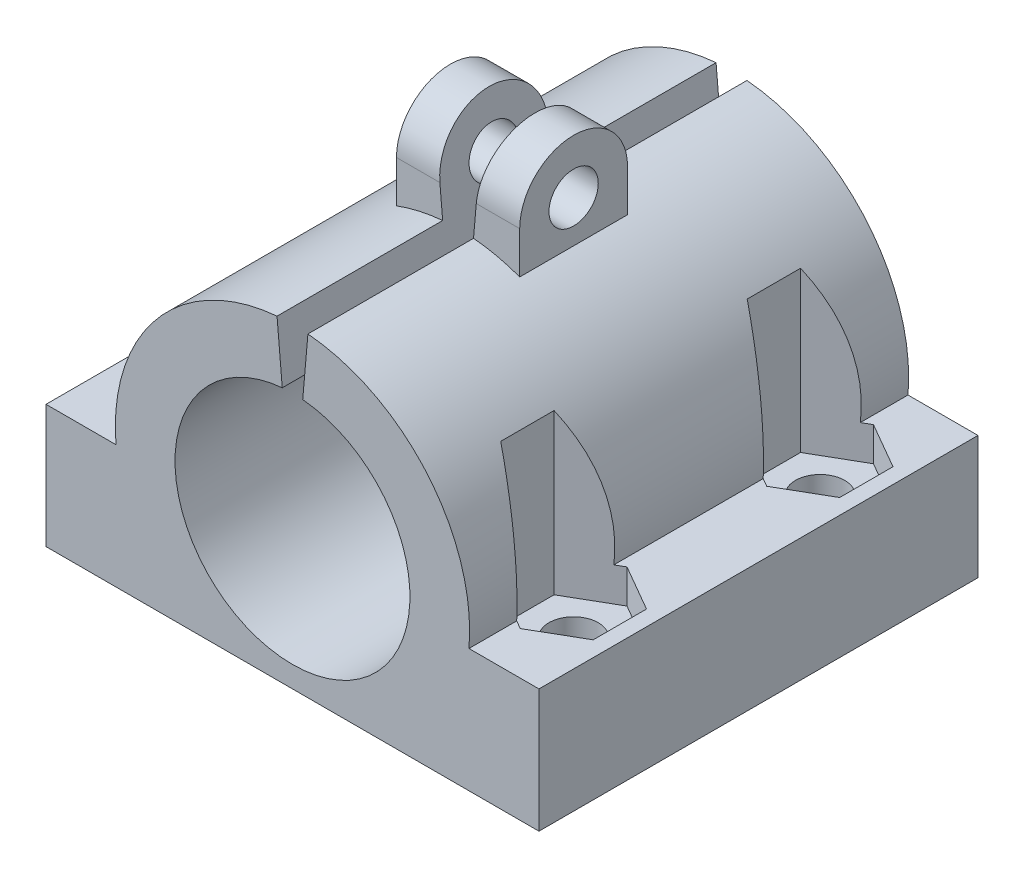
SolidWorks part; units mm, degrees
ref_plane "Front Plane" through (0, 0, 0) normal (0, 0, 1) x (1, 0, 0)
ref_plane "Top Plane" through (0, 0, 0) normal (0, 1, 0) x (1, 0, 0)
ref_plane "Right Plane" through (0, 0, 0) normal (1, 0, 0) x (0, 0, -1)
sketch "Sketch1" plane through (0, 0, 0) normal (0, 1, 0) x (1, 0, 0)
  line L1 (-16, 14.25) -> (16, 14.25)
  line L2 (-16, 14.25) -> (-16, -14.25)
  line L3 (-16, -14.25) -> (16, -14.25)
  line L4 (16, 14.25) -> (16, -14.25)
  line L5 (-16, 14.25) -> (16, -14.25) construction
  line L6 (-16, -14.25) -> (16, 14.25) construction
  point P0 (0, 0)
  dimension "D1" = 32
  dimension "D2" = 28.5
extrude "Boss-Extrude1" add sketch "Sketch1" along normal blind 8
sketch "Sketch3" plane through (0, 0, 14.25) normal (0, 0, 1) x (1, 0, 0)
  line L0 (0, 0) -> (0, 9) construction
  line L1 (-16, 0) -> (16, 0) construction
  line L2 (-7.1589, 0) -> (7.1589, 0)
  arc A0 (7.1589, 0) -> (-7.1589, 0) centre (0, 9) ccw
  dimension "D1" = 23
  dimension "D2" = 9
extrude "Boss-Extrude2" add sketch "Sketch3" against normal through all contours A0 L2
sketch "Sketch4" plane through (0, 0, 14.25) normal (0, 0, 1) x (1, 0, 0)
  line L0 (0, 20.5) -> (0, 0) construction
  line L1 (0, 9) -> (-11.5, 9) construction
  arc A0 (11.4564, 8) -> (-11.4564, 8) centre (0, 9) ccw construction
  circle A1 centre (0, 9) radius 7.625
  dimension "D1" = 15.25
  dimension "D2" = 0
extrude "Cut-Extrude2" cut sketch "Sketch4" against normal offset from surface (26.5 mm away) 2 up to face at (0, 7.4167, -14.25)
sketch "Sketch5" plane through (0, 0, -14.25) normal (0, 0, -1) x (-1, 0, 0)
  line L0 (0, 0) -> (0, 20.5) construction
  line L1 (7.625, 9) -> (-7.625, 9) construction
  arc A0 (11.4564, 8) -> (-11.4564, 8) centre (0, 9) ccw construction
  circle A1 centre (0, 9) radius 6
  circle A2 centre (0, 9) radius 7.625 construction
  circle A3 centre (0, 9) radius 7.625 construction
  dimension "D1" = 12
  dimension "D2" = 0
extrude "Cut-Extrude3" cut sketch "Sketch5" against normal through all
sketch "Sketch2" plane through (0, 8, 0) normal (0, 1, 0) x (1, 0, 0)
  line L0 (0, -14.25) -> (0, 14.25) construction
  line L1 (0, 0) -> (-16, 0) construction
  line L2 (-16, 14.25) -> (-16, -14.25) construction
  line L5 (-11.5, -14.25) -> (11.5, -14.25) construction
  line L6 (11.5, 14.25) -> (-11.5, 14.25) construction
  circle A0 centre (-12, 8) radius 1.6
  circle A1 centre (12, 8) radius 1.6
  circle A2 centre (12, -8) radius 1.6
  circle A3 centre (-12, -8) radius 1.6
  dimension "D3" = 3.2
  dimension "D1" = 12
  dimension "D2" = 8
extrude "Cut-Extrude1" cut sketch "Sketch2" against normal through all and the other way through all
sketch "Sketch6" plane through (0, 8, 0) normal (0, 1, 0) x (1, 0, 0)
  line L0 (-16, 0) -> (16, 0) construction
  line L1 (-16, 14.25) -> (-16, -14.25) construction
  line L2 (16, -14.25) -> (16, 14.25) construction
  line L3 (0, 14.25) -> (0, -14.25) construction
  line L4 (11.5, 14.25) -> (-11.5, 14.25) construction
  line L5 (-11.5, -14.25) -> (11.5, -14.25) construction
  line L6 (-12, 8) -> (-12, 11.4641) construction
  line L7 (-12, 11.4641) -> (-15, 9.7321)
  line L8 (-15, 9.7321) -> (-15, 6.2679)
  line L9 (-15, 6.2679) -> (-12, 4.5359)
  line L10 (-12, 4.5359) -> (-9, 6.2679)
  line L11 (-9, 6.2679) -> (-9, 9.7321)
  line L12 (-9, 9.7321) -> (-12, 11.4641)
  line L13 (-12, -8) -> (-12, -11.4641) construction
  line L14 (-9, -9.7321) -> (-12, -11.4641)
  line L15 (-9, -6.2679) -> (-9, -9.7321)
  line L16 (-12, -4.5359) -> (-9, -6.2679)
  line L17 (-15, -6.2679) -> (-12, -4.5359)
  line L18 (-15, -9.7321) -> (-15, -6.2679)
  line L19 (-12, -11.4641) -> (-15, -9.7321)
  line L20 (12, -8) -> (12, -11.4641) construction
  line L21 (12, 8) -> (12, 11.4641) construction
  line L22 (12, -11.4641) -> (15, -9.7321)
  line L23 (15, -9.7321) -> (15, -6.2679)
  line L24 (15, -6.2679) -> (12, -4.5359)
  line L25 (12, -4.5359) -> (9, -6.2679)
  line L26 (9, -6.2679) -> (9, -9.7321)
  line L27 (9, -9.7321) -> (12, -11.4641)
  line L28 (9, 9.7321) -> (12, 11.4641)
  line L29 (9, 6.2679) -> (9, 9.7321)
  line L30 (12, 4.5359) -> (9, 6.2679)
  line L31 (15, 6.2679) -> (12, 4.5359)
  line L32 (15, 9.7321) -> (15, 6.2679)
  line L33 (12, 11.4641) -> (15, 9.7321)
  circle A0 centre (-12, 8) radius 3 construction
  circle A1 centre (-12, -8) radius 3 construction
  circle A2 centre (12, -8) radius 3 construction
  circle A3 centre (12, 8) radius 3 construction
  circle A4 centre (-12, 8) radius 1.6 construction
  dimension "D2" = 0
  dimension "D1" = 6
extrude "Cut-Extrude4" cut sketch "Sketch6" along normal through all and the other way blind 2.2
sketch "Sketch8" plane through (0, 0, 0) normal (1, 0, 0) x (0, 0, -1)
  line L0 (0, 0) -> (0, 22.5) construction
  line L1 (-3.5, 22.5) -> (-3.5, 18.5)
  line L2 (-3.5, 18.5) -> (3.5, 18.5)
  line L3 (3.5, 18.5) -> (3.5, 22.5)
  line L4 (14.25, 20.5) -> (-14.25, 20.5) construction
  arc A0 (3.5, 22.5) -> (-3.5, 22.5) centre (0, 22.5) ccw
  circle A1 centre (0, 22.5) radius 1.6
  dimension "D1" = 7
  dimension "D4" = 3.2
  dimension "D2" = 2
  dimension "D3" = 4
extrude "Boss-Extrude3" add sketch "Sketch8" along normal blind 4 and the other way blind 4
sketch "Sketch9" plane through (0, 0, 14.25) normal (0, 0, 1) x (1, 0, 0)
  line L0 (0, 31) -> (0, 9) construction
  line L1 (0, 9) -> (1.7431, 28.9239)
  line L2 (0, 9) -> (-1.7431, 28.9239)
  arc A1 (1.7431, 28.9239) -> (-1.7431, 28.9239) centre (0, 9) ccw
  dimension "D2" = 40
  dimension "D1" = 5
extrude "Cut-Extrude5" cut sketch "Sketch9" against normal through all
equation "\"X-ROD-SPACING\"=45"
equation "\"Y-ROD-SPACING\"=75"
equation "\"Z-ROD-SPACING\"=17.5"
equation "\"Y-BED-OFFSET\"=2"
equation "\"Y-BED-ROD-INSET\"=3.5"
equation "\"T-SLOT-NUT-FILLET-RADIUS\"=0.25"
equation "\"T-SLOT-SCREW-SHAFT-RADIUS\"=1.75"
equation "\"T-SLOT-SCREW-SHAFT-CUTOUT-LENGTH\"=10.5"
equation "\"T-SLOT-NUT-DEPTH\"=4.2"
equation "\"T-SLOT-NUT-WIDTH\"=3"
equation "\"T-SLOT-NUT-END-DISTANCE\"=8"
equation "\"ACRYLIC-THICKNESS\"=10"
equation "\"ACRYLIC-THICKNESS2\"=4.5"
equation "\"ACRYLIC-TAB-CUTOUT-SIZE\"=\"ACRYLIC-THICKNESS\"+\"ACRYLIC-TAB-TOLERANCE\"*2"
equation "\"ACRYLIC-TAB-WIDTH\"=\"ACRYLIC-THICKNESS\""
equation "\"ACRYLIC-M3-HOLE\"=3.1"
equation "\"SMOOTHROD-CAP-SCREW-DISTANCE\"=20"
equation "\"FRAME-WIDTH-INNER\"=370"
equation "\"NEMA17-HOLE-SPACING\"=31"
equation "\"NEMA17-CENTRAL-CUTOUT\"=22.5"
equation "\"Z-BRACKET-REACH\"=55"
equation "\"TOP-BRACKET-SPACING\"=40"
equation "\"SMOOTHROD-X-LENGTH\"=350"
equation "\"SMOOTHROD-Y-LENGTH\"=350"
equation "\"SMOOTHROD-Z-LENGTH\"=350"
equation "\"SMOOTHROD-TIGHTENING-HEADROOM\"=.25"
equation "\"LEADSCREW-Z-LENGTH\"=300"
equation "\"SCREW-LENGTH-FRAME\"=\"ACRYLIC-THICKNESS\" + 10"
equation "\"SCREW-HEAD-RADIUS\"=6"
equation "\"PRINTED-X-SMOOTHROD-DIAMETER\"=8.2"
equation "\"PRINTED-X-SMOOTHROD-CUTOUT\"=10"
equation "\"PRINTED-X-BASE-HEIGHT\"=10"
equation "\"PRINTED-LM8UU-CUTOUT-SIZE\"=15.25"
equation "\"PRINTED-LM8UU-CUTOUT-LENGTH\"=24.5"
equation "\"PRINTED-X-IDLER-HEIGHT\"=16"
equation "\"PSU-MOUNTING-WIDTH\"=95"
equation "\"PSU-MOUNTING-HEIGHT\"=177"
equation "\"Y-BELT-TO-ROD-DISTANCE\"=20"
equation "\"D3@Sketch2\"=3.2"
equation "\"D1@Sketch4\"=\"PRINTED-LM8UU-CUTOUT-SIZE\""
equation "\"D1@Sketch6\"=\"T-SLOT-NUT-WIDTH\"*2"
